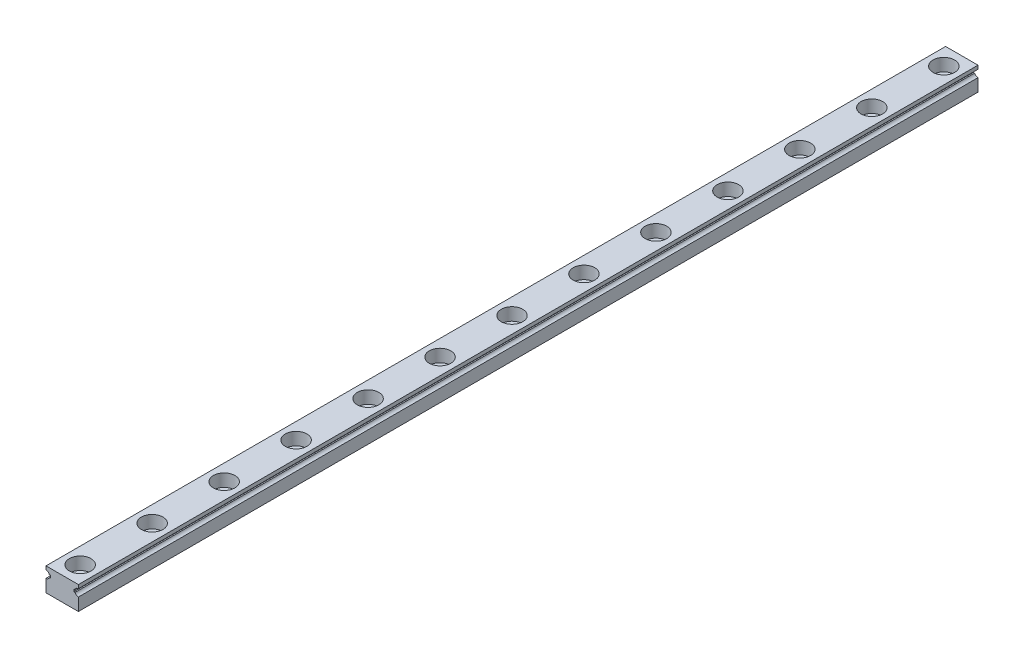
SolidWorks part; units mm, degrees
ref_plane "Спереди" through (0, 0, 0) normal (0, 0, 1) x (1, 0, 0)
ref_plane "Сверху" through (0, 0, 0) normal (0, 1, 0) x (1, 0, 0)
ref_plane "Справа" through (0, 0, 0) normal (1, 0, 0) x (0, 0, -1)
sketch "Sketch1" plane through (0, 0, 0) normal (0, 0, 1) x (1, 0, 0)
  line L0 (0, 0) -> (0, 5.7299) construction
  line L1 (-4.5, -3.25) -> (4.5, -3.25)
  line L2 (-4.5, -3.25) -> (-4.5, 0.25)
  line L3 (-4.5, 3.25) -> (4.5, 3.25)
  line L4 (4.5, -3.25) -> (4.5, 0.25)
  line L5 (-4.5, -3.25) -> (4.5, 3.25) construction
  line L6 (-4.5, 3.25) -> (4.5, -3.25) construction
  line L7 (-4.5, 2.25) -> (-4.5, 3.25)
  line L8 (-3.564, 0.898) -> (-3.2351, 0.898)
  line L9 (3.564, 0.898) -> (3.2351, 0.898)
  line L10 (-3.564, 1.602) -> (-3.2351, 1.602)
  line L11 (-3.2351, 0.898) -> (-3.2351, 1.602)
  line L12 (3.2351, 0.898) -> (3.2351, 1.602)
  line L13 (3.564, 1.602) -> (3.2351, 1.602)
  line L14 (4.5, 2.25) -> (4.5, 3.25)
  arc A0 (-3.564, 1.602) -> (-4.5, 2.25) centre (-4.5, 1.25) ccw
  arc A1 (-4.5, 0.25) -> (-3.564, 0.898) centre (-4.5, 1.25) ccw
  arc A2 (4.5, 0.25) -> (3.564, 0.898) centre (4.5, 1.25) cw
  arc A3 (3.564, 1.602) -> (4.5, 2.25) centre (4.5, 1.25) cw
  point P0 (0, 0)
  dimension "D3" = 1
  dimension "D1" = 9
  dimension "D2" = 6.5
  dimension "D4" = 2
extrude "Extrude1" add sketch "Sketch1" along normal blind 250
sketch "Sketch2" plane through (0, 3.25, 0) normal (0, 1, 0) x (1, 0, 0)
  line L0 (4.5, 0) -> (-4.5, 0) construction
  circle A0 centre (0, -5) radius 1.75
  circle A1 centre (0, -5) radius 3
  dimension "D1" = 3.5
  dimension "D2" = 6
  dimension "D3" = 5
extrude "Extrude2" cut sketch "Sketch2" against normal blind 3.5 contours A1
extrude "Extrude3" cut sketch "Sketch" against normal through all contours A0
sketch "Sketch" plane through (0, 3.25, 0) normal (0, 1, 0) x (1, 0, 0) same geometry as "Sketch2"
pattern_linear "LPattern1" count 13 spacing 20 along (0, 0, 1) of "Extrude2", "Extrude3"
